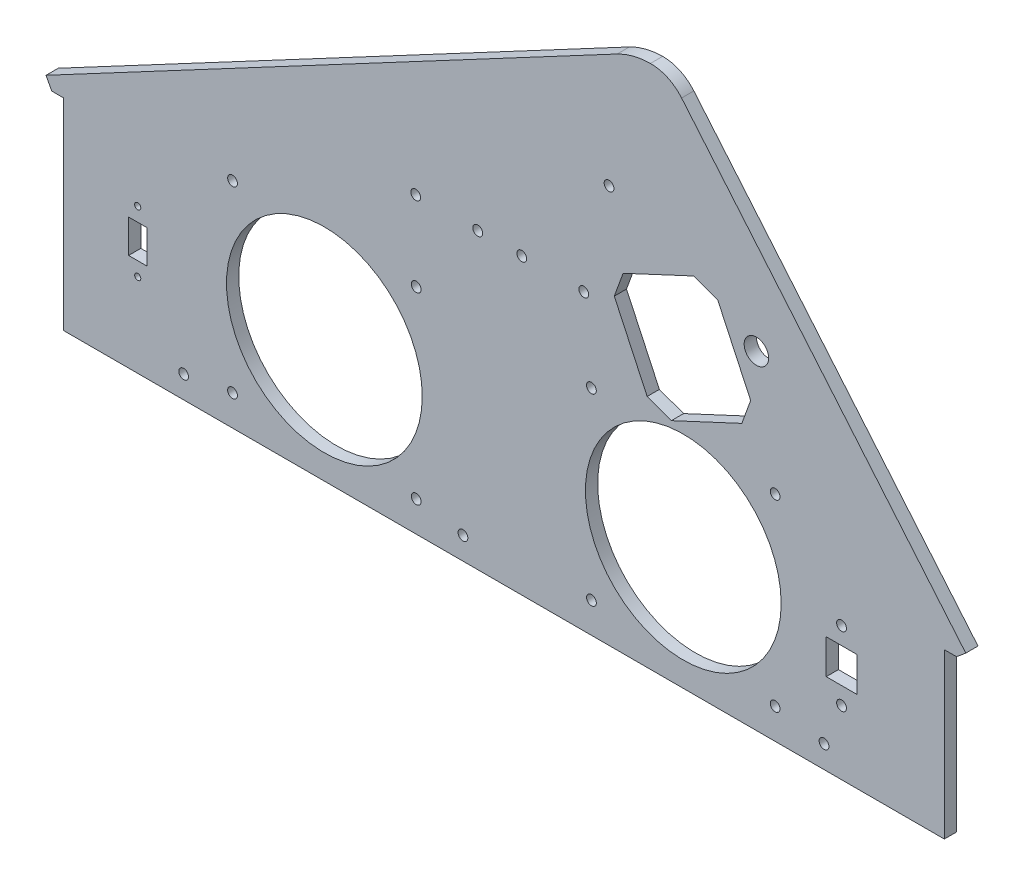
SolidWorks part; units mm, degrees
ref_plane "Front (1)" through (0, 0, 0) normal (0, 0, 1) x (1, 0, 0)
ref_plane "Top (2)" through (0, 0, 0) normal (0, 1, 0) x (1, 0, 0)
ref_plane "Right (3)" through (0, 0, 0) normal (1, 0, 0) x (0, 0, -1)
ref_axis "X-Axis" through (-80.9, 0, 0) along (1, 0, 0)
ref_axis "Y-Axis" through (0, -50, 0) along (0, 1, 0)
ref_axis "Z-Axis" through (0, 0, 50) along (0, 0, -1)
sketch "Sketch1" plane through (0, 0, 0) normal (0, 0, 1) x (1, 0, 0)
  line L0 (342.9, 76.8001) -> (231.5705, 209.4774)
  line L1 (0, 0) -> (342.9, 0)
  line L2 (115.7853, 147.8485) -> (194.4804, 0) construction
  line L3 (231.5705, 209.4774) -> (0, 86.2195)
  line L4 (342.9, 0) -> (342.9, 76.8001)
  line L5 (0, 86.2195) -> (0, 0)
  line L7 (215.5537, 200.9521) -> (228.5029, 204.2528) construction
  line L8 (287.2353, 143.1387) -> (116.6492, 0) construction
  line L9 (240.6423, 198.6661) -> (228.5029, 204.2528) construction
  line L17 (342.9, 76.8001) -> (351.2464, 66.8533)
  line L18 (347.6625, 63.8461) -> (342.9, 63.8461)
  line L19 (347.6625, 63.8461) -> (351.2464, 66.8533)
  line L20 (0, 78.4247) -> (-4.5085, 78.4247)
  line L21 (-4.5085, 78.4247) -> (-6.7462, 82.6287)
  line L22 (-6.7462, 82.6287) -> (0, 86.2195)
  arc A0 (215.5537, 200.9521) -> (228.5029, 204.2528) centre (228.7855, 176.0928) cw
  arc A1 (228.5029, 204.2528) -> (240.6423, 198.6661) centre (228.6598, 188.6116) cw
  dimension "D1" = 342.9
  dimension "D2" = 222.6843
  dimension "D3" = 50
  dimension "D4" = 28.025
  dimension "D5" = 167.4876
  dimension "D6" = 198.6661
  dimension "D7" = 200.9521
  dimension "D8" = 12.954
  dimension "D9" = 4.7625
  dimension "D10" = 4.5085
  dimension "D11" = 4.7625
extrude "Boss-Extrude1" add sketch "Sketch1" along normal blind 4.7625 contours L0 L3 L5 L1 L4 | L18 L19 L17 L4 | L22 L21 L20 L5 region at (178.4372, 77.6023, 0) region at (345.8678, 68.6614, 0) region at (-2.6469, 81.7359, 0)
sketch "Sketch2" plane through (0, 0, 4.7625) normal (0, 0, 1) x (1, 0, 0)
  line L0 (342.9, 0) -> (342.9, 63.8461) construction
  line L2 (0, 0) -> (342.9, 0) construction
  line L4 (342.9, 0) -> (342.9, 63.8461) construction
  circle A4 centre (46.8249, 8.7312) radius 1.905
  circle A5 centre (296.0751, 8.7312) radius 1.905
  circle A6 centre (155.5496, 8.7312) radius 1.905
  circle A7 centre (212.4139, 154.94) radius 1.905
  dimension "D10" = 3.81
  dimension "D6" = 140.5255
  dimension "D2" = 46.8249
  dimension "D3" = 8.7312
  dimension "D4" = 130.4862
  dimension "D5" = 146.2088
  dimension "D7" = 249.2502
extrude "Cut-Extrude1" cut sketch "Sketch2" against normal through all
sketch "Sketch3" plane through (0, 0, 4.7625) normal (0, 0, 1) x (1, 0, 0)
  line L0 (65.85, 83.375) -> (101.6, 47.625) construction
  line L1 (101.6, 47.625) -> (137.35, 11.875) construction
  line L4 (171.45, 177.4771) -> (171.45, 0) construction
  line L5 (241.3, 47.625) -> (205.55, 11.875) construction
  line L6 (277.05, 83.375) -> (241.3, 47.625) construction
  line L8 (0, 78.4247) -> (0, 0) construction
  line L9 (0, 0) -> (342.9, 0) construction
  line L10 (215.5537, 200.9521) -> (-6.7462, 82.6287) construction
  circle A0 centre (101.6, 47.625) radius 38.1
  circle A1 centre (137.35, 83.375) radius 1.905
  circle A2 centre (65.85, 83.375) radius 1.905
  circle A3 centre (65.85, 11.875) radius 1.905
  circle A4 centre (137.35, 11.875) radius 1.905
  circle A6 centre (205.55, 11.875) radius 1.905
  circle A7 centre (277.05, 11.875) radius 1.905
  circle A8 centre (277.05, 83.375) radius 1.905
  circle A9 centre (205.55, 83.375) radius 1.905
  circle A10 centre (241.3, 47.625) radius 38.1
  dimension "D3" = 76.2
  dimension "D4" = 3.81
  dimension "D1" = 71.5
  dimension "D2" = 71.5
  dimension "D5" = 101.6
  dimension "D6" = 47.625
extrude "Cut-Extrude2" cut sketch "Sketch3" against normal through all
sketch "Sketch4" plane through (0, 0, 4.7625) normal (0, 0, 1) x (1, 0, 0)
  line L1 (296.926, 45.212) -> (308.864, 45.212)
  line L2 (296.926, 45.212) -> (296.926, 31.75)
  line L3 (296.926, 31.75) -> (308.864, 31.75)
  line L4 (308.864, 45.212) -> (308.864, 31.75)
  line L6 (302.895, 51.943) -> (302.895, 45.212) construction
  line L7 (302.895, 45.212) -> (302.895, 31.75) construction
  line L8 (302.895, 31.75) -> (302.895, 25.019) construction
  line L9 (0, 0) -> (342.9, 0) construction
  line L10 (342.9, 0) -> (342.9, 63.8461) construction
  circle A0 centre (302.895, 51.943) radius 1.905
  circle A1 centre (302.895, 25.019) radius 1.905
  dimension "D6" = 26.924
  dimension "D7" = 3.81
  dimension "D1" = 11.938
  dimension "D2" = 13.462
  dimension "D4" = 31.75
  dimension "D5" = 40.005
extrude "Cut-Extrude3" cut sketch "Sketch4" against normal through all
sketch "Sketch5" plane through (0, 0, 4.7625) normal (0, 0, 1) x (1, 0, 0)
  line L2 (0, 0) -> (342.9, 0) construction
  circle A1 centre (137.16, 114.3) radius 1.905
  circle A5 centre (161.29, 114.3) radius 1.905
  circle A6 centre (178.435, 114.3) radius 1.905
  circle A7 centre (202.565, 114.3) radius 1.905
  dimension "D7" = 3.81
  dimension "D1" = 114.3
  dimension "D2" = 202.565
  dimension "D3" = 24.13
  dimension "D4" = 41.275
  dimension "D5" = 41.275
extrude "Cut-Extrude4" cut sketch "Sketch5" against normal through all
sketch "Sketch6" plane through (0, 0, 4.7625) normal (0, 0, 1) x (1, 0, 0)
  line L1 (25.4, 50.927) -> (32.512, 50.927)
  line L2 (25.4, 50.927) -> (25.4, 37.973)
  line L3 (25.4, 37.973) -> (32.512, 37.973)
  line L4 (32.512, 50.927) -> (32.512, 37.973)
  line L5 (0, 78.4247) -> (0, 0) construction
  line L6 (32.512, 44.45) -> (25.4, 44.45) construction
  line L8 (28.956, 32.55) -> (28.956, 44.45) construction
  line L9 (28.956, 44.45) -> (28.956, 56.35) construction
  line L10 (0, 0) -> (342.9, 0) construction
  circle A0 centre (28.956, 56.35) radius 1.1938
  circle A1 centre (28.956, 32.55) radius 1.1938
  dimension "D5" = 2.3876
  dimension "D6" = 23.8
  dimension "D1" = 7.112
  dimension "D2" = 12.954
  dimension "D3" = 25.4
  dimension "D4" = 44.45
extrude "Cut-Extrude5" cut sketch "Sketch6" against normal through all
sketch "Sketch7" plane through (0, 0, 0) normal (0, 0, -1) x (-1, 0, 0)
  line L0 (0, 6.35) -> (-63.5, 6.35) construction
  line L1 (0, 78.4247) -> (0, 0) construction
  line L2 (0, 0) -> (-342.9, 0) construction
  text T0 "LCSAP-606"
  dimension "D1" = 63.5
  dimension "D2" = 6.35
extrude "Cut-Extrude6" cut sketch "Sketch7" against normal blind 1.016
sketch "Sketch8" plane through (0, 0, 4.7625) normal (0, 0, 1) x (1, 0, 0)
  line L0 (217.8748, 128.206) -> (245.3048, 140.9969)
  line L1 (245.3048, 140.9969) -> (254.7298, 137.5665)
  line L2 (254.7298, 137.5665) -> (267.5206, 110.1364)
  line L3 (267.5206, 110.1364) -> (264.0902, 100.7115)
  line L4 (264.0902, 100.7115) -> (236.6602, 87.9206)
  line L5 (236.6602, 87.9206) -> (227.2352, 91.351)
  line L6 (227.2352, 91.351) -> (214.4444, 118.7811)
  line L7 (214.4444, 118.7811) -> (217.8748, 128.206)
  line L8 (231.5898, 134.6014) -> (240.9825, 114.4588) construction
  line L9 (240.9825, 114.4588) -> (261.1252, 123.8514) construction
  line L11 (347.6625, 0) -> (-4.7625, 0) construction
  line L12 (342.9, 0) -> (342.9, 63.8175) construction
  line L13 (0, 0) -> (342.9, 0) construction
  dimension "D1" = 44.45
  dimension "D2" = 52.832
  dimension "D3" = 135
  dimension "D4" = 25
  dimension "D5" = 101.9175
  dimension "D6" = 114.4587
extrude "Cut-Extrude7" cut sketch "Sketch8" against normal through all
sketch "Sketch9" plane through (0, 0, -406.4) normal (0, 0, 1) x (1, 0, 0)
  line L0 (269.7578, 127.8769) -> (261.1252, 123.8514) construction
  line L1 (267.5206, 110.1364) -> (254.7298, 137.5665) construction
  circle A0 centre (269.7578, 127.8769) radius 4.7625
  dimension "D1" = 9.525
  dimension "D2" = 9.525
extrude "Cut-Extrude13" cut sketch "Sketch9" along normal through all contours A0
